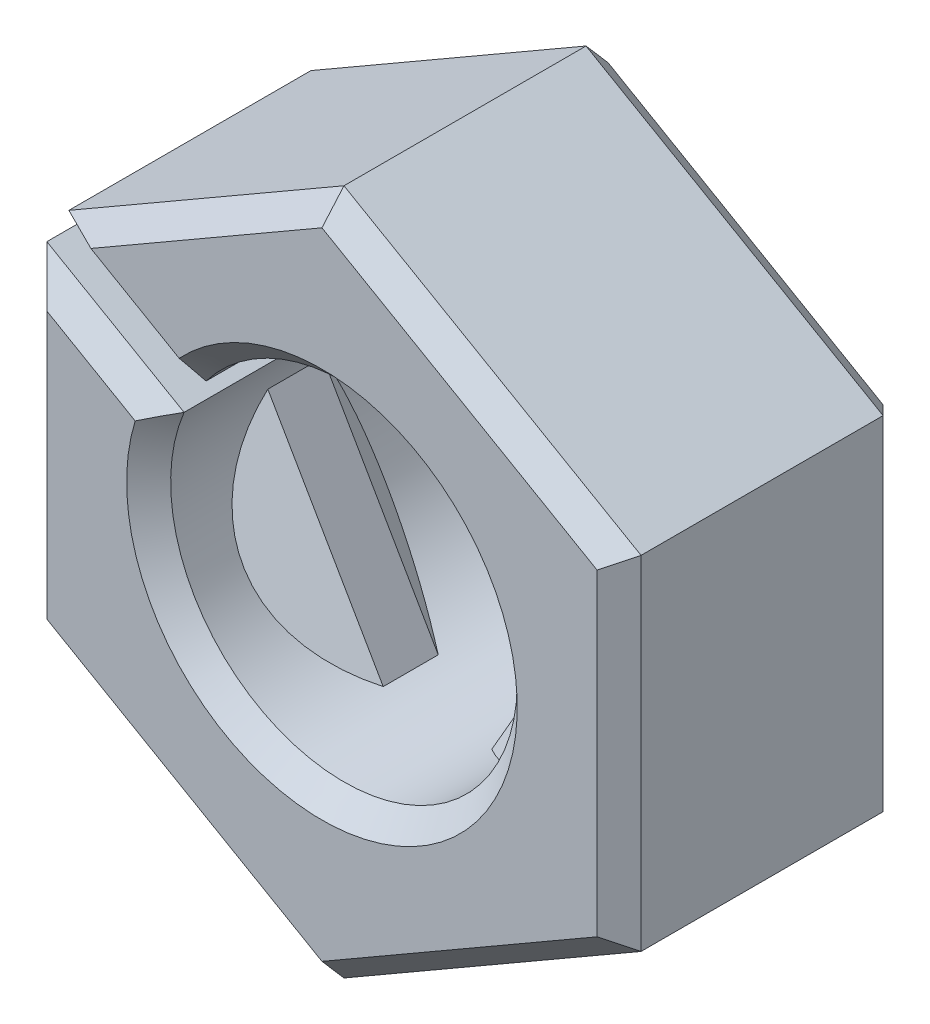
SolidWorks part; units mm, degrees
ref_plane "Front" through (0, 0, 0) normal (0, 0, 1) x (1, 0, 0)
ref_plane "Top" through (0, 0, 0) normal (0, 1, 0) x (1, 0, 0)
ref_plane "Right" through (0, 0, 0) normal (1, 0, 0) x (0, 0, -1)
sketch "Sketch1" plane through (0, 0, 0) normal (0, 0, 1) x (1, 0, 0)
  line L1 (2.7, -1.5588) -> (2.7, 1.5588)
  line L2 (2.7, 1.5588) -> (0, 3.1177)
  line L3 (0, 3.1177) -> (-2.7, 1.5588)
  line L4 (-2.7, 1.5588) -> (-2.7, -1.5588)
  line L5 (-2.7, -1.5588) -> (0, -3.1177)
  line L6 (0, -3.1177) -> (2.7, -1.5588)
  circle A0 centre (0, 0) radius 2.7 construction
  circle A1 centre (0, 0) radius 1.575
  dimension "D1" = 3.15
  dimension "D2" = 5.4
extrude "Boss-Extrude1" add sketch "Sketch1" along normal mid plane 2.6
sketch "Sketch3" plane through (0, 0, 0) normal (1, 0, 0) x (0, 0, -1)
  line L0 (-0.65, 1.575) -> (0.65, 1.575)
  line L1 (1.3, 1.575) -> (-1.3, 1.575) construction
  line L4 (0, 0) -> (0, 1.175) construction
  line L5 (0.65, 1.575) -> (0.25, 1.175)
  line L6 (0.25, 1.175) -> (-0.25, 1.175)
  line L7 (-0.25, 1.175) -> (-0.65, 1.575)
  dimension "D1" = 0.4
  dimension "D2" = 90
  dimension "D3" = 0.5
extrude "Clip" add sketch "Sketch3" along normal up to next and the other way up to next
pattern_circular "Clips x3" count 3 over 360 about axis through (0, 0, 1.3) along (0, 0, 1) of "Clip"
sketch "Sketch4" plane through (0, 0, 0) normal (0, 0, 1) x (1, 0, 0)
  line L0 (-2.7, 1.5588) -> (0, 0)
extrude "Split" cut sketch "Sketch4" against normal through all both and the other way through all thin thin type mid plane wall 0.4
chamfer "Deburs" distance 0.2 angle 45 18 edges at (1.364, -0.7875, -1.3) (2.7, 0, -1.3) (1.35, 2.3383, -1.3) (-1.25, 2.396, -1.3) (-2.7, -0.1155, -1.3) (-1.35, -2.3383, -1.3) (1.35, -2.3383, -1.3) (1.364, -0.7875, 1.3) (-1.35, -2.3383, 1.3) (-2.7, -0.1155, 1.3) (-1.25, 2.396, 1.3) (1.35, 2.3383, 1.3) (2.7, 0, 1.3) (1.35, -2.3383, 1.3) (-1.8765, 1.3143, -1.3) (-2.0765, 0.9679, -1.3) (-1.8765, 1.3143, 1.3) (-2.0765, 0.9679, 1.3)
equation "\"D1@Sketch1\" = 3.15mm 'was: \"Clearance Hole Diameter@Box Assy.Assembly\""
equation "\"D2@Sketch1\" = 5.7mm-0.3mm 'was: \"Nut Trap Diameter@Box Assy.Assembly\"-0.3mm"
equation "\"D1@Boss-Extrude1\" = 2.6mm 'was: \"Nut Trap Depth@Box Assy.Assembly\""
